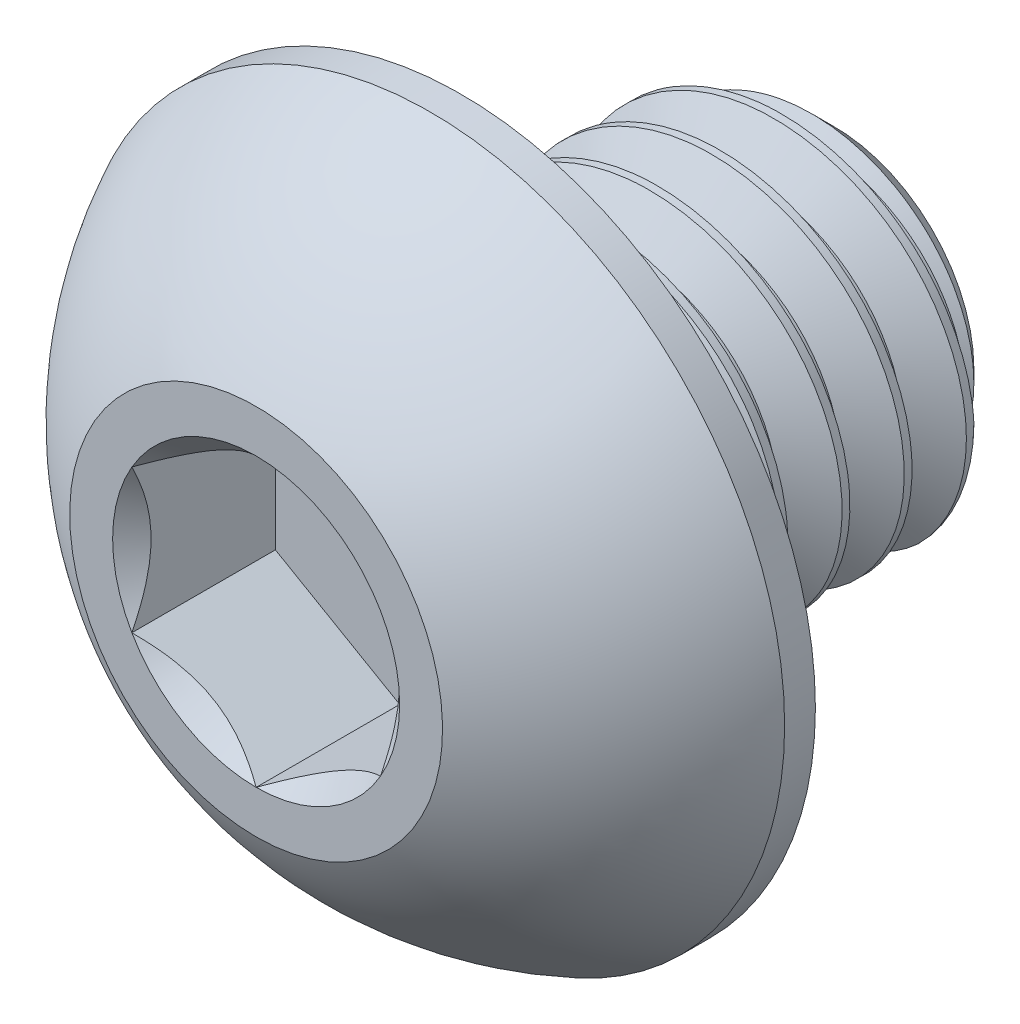
SolidWorks part; units mm, degrees
ref_plane "Front" through (0, 0, 0) normal (0, 0, 1) x (1, 0, 0)
ref_plane "Top" through (0, 0, 0) normal (0, 1, 0) x (1, 0, 0)
ref_plane "Right" through (0, 0, 0) normal (1, 0, 0) x (0, 0, -1)
sketch "Sketch1" plane through (0, 0, 0) normal (1, 0, 0) x (0, 0, -1)
  line L2 (1.65, 1.5) -> (4.65, 1.5)
  line L3 (4.65, 1.5) -> (4.65, 0)
  line L4 (4.65, 0) -> (1.65, 0)
  line L6 (1.4025, 2.85) -> (1.65, 2.85) construction
  line L7 (4.65, 1.5) -> (4.65, -1.5) construction
  line L8 (0, 0) -> (1.65, 0) construction
  line L9 (1.65, 2.85) -> (1.65, -2.85) construction
  line L11 (1.65, 1.5) -> (1.65, 0)
  line L13 (0, 1) -> (0, -1) construction
  line L14 (0, 1) -> (0, 1.5) construction
  line L15 (4.6187, 1.5541) -> (4.8687, 1.1211) construction
  line L16 (4.8687, 1.1211) -> (5.1187, 1.5541) construction
  line L17 (5.1187, 1.5541) -> (4.6187, 1.5541) construction
  line L18 (4.65, 1.5) -> (5.0875, 1.5) construction
  line L19 (4.8687, 1.5541) -> (4.8687, 1.5) construction
  line L20 (4.8687, 1.5) -> (4.8687, 1.1752) construction
  line L21 (4.8687, 1.1752) -> (4.8687, 1.1211) construction
  line L22 (4.8375, 1.1752) -> (4.9, 1.1752)
  line L23 (4.6344, 1.5271) -> (5.1031, 1.5271)
  line L24 (4.9, 1.1752) -> (5.1031, 1.5271)
  line L25 (4.8375, 1.1752) -> (4.6344, 1.5271)
  line L26 (4.275, 1.5) -> (4.65, 1.125)
  arc A3 (0, 1.5) -> (1.4025, 2.85) centre (2.7948, 0) cw construction
  point P29 (4.8687, 1.5271)
  point P30 (3.4, -1.5)
  dimension "D1" = 0.2475
  dimension "Pitch" = 0.5
  dimension "D3" = 0.0625
  dimension "D2" = 0.375
  dimension "D4" = 45
  dimension "D5" = 1.25
sketch "Sketch10" plane through (0, 0, 0) normal (1, 0, 0) x (0, 0, -1)
  line L0 (4.275, 1.5) -> (4.65, 1.125) construction
  line L1 (4.275, 1.5) -> (4.65, 1.125)
  line L4 (4.65, 1.5) -> (1.65, 1.5)
  line L5 (4.65, 0) -> (4.65, 1.5)
  line L6 (1.65, 0) -> (4.65, 0)
  line L7 (1.65, 1.5) -> (1.65, 0)
  line L8 (4.275, 1.5) -> (1.65, 1.5)
  line L9 (4.65, 0) -> (4.65, 1.125)
  line L10 (1.65, 0) -> (4.65, 0)
  line L11 (1.65, 1.5) -> (1.65, 0)
  dimension "D1" = 0
revolve "Revolve3" add sketch "Sketch10" angle 360 about L8
sketch "Sketch7" plane through (0, 0, 0) normal (1, 0, 0) x (0, 0, -1)
  line L6 (1.4025, 2.85) -> (1.65, 2.85) construction
  line L8 (0, 0) -> (1.65, 0) construction
  line L11 (1.65, 2.85) -> (1.65, -2.85) construction
  line L12 (1.4025, 2.85) -> (1.65, 2.85)
  line L13 (0, 0) -> (1.65, 0)
  line L14 (0, 1) -> (0, -1) construction
  line L15 (1.65, 2.85) -> (1.65, 0)
  line L16 (0, 1.5) -> (0, 0)
  arc A2 (1.4025, 2.85) -> (0, 1.5) centre (2.7948, 0) ccw construction
  arc A3 (1.4025, 2.85) -> (0, 1.5) centre (2.7948, 0) ccw
revolve "Revolve2" add sketch "Sketch7" angle 360 mid plane about L13
sketch "Sketch5" plane through (0, 0, 0) normal (0, 0, 1) x (1, 0, 0)
  line L1 (1, -0.5774) -> (1, 0.5774)
  line L2 (1, 0.5774) -> (0, 1.1547)
  line L3 (0, 1.1547) -> (-1, 0.5774)
  line L4 (-1, 0.5774) -> (-1, -0.5774)
  line L5 (-1, -0.5774) -> (0, -1.1547)
  line L6 (0, -1.1547) -> (1, -0.5774)
  circle A0 centre (0, 0) radius 1 construction
extrude "Cut-Extrude2" cut sketch "Sketch5" against normal blind 1.155
sketch "Sketch6" plane through (0, 0, 0) normal (0, 0, 1) x (1, 0, 0)
  circle A0 centre (0, 0) radius 1.1547
extrude "Cut-Extrude3" cut sketch "Sketch6" against normal blind 1.155 draft 45
sketch "Sketch9" plane through (0, 0, -1.65) normal (0, 0, -1) x (-1, 0, 0)
  circle A0 centre (0, 0) radius 1.5 construction
  circle A4 centre (0, 0) radius 1.5
split "Split1" bodies to split 113 resulting bodies 123 124 split by face at (2.85, 0, -1.65)
sketch "Sketch11" plane through (0, 0, -4.65) normal (0, 0, -1) x (-1, 0, 0)
  circle A0 centre (0, 0) radius 1.5 construction
  circle A1 centre (0, 0) radius 1.5
curve "Helix/Spiral1" pitch 0.5 height 4.65 radius 1.5 centre (0, 0, -4.65) axis (0, 0, 1) start towards (0, 1, 0)
sketch "Sketch12" plane through (0, 0, 0) normal (1, 0, 0) x (0, 0, -1)
  line L0 (4.8375, 1.1752) -> (4.9, 1.1752) construction
  line L1 (4.9, 1.1752) -> (5.1031, 1.5271) construction
  line L2 (4.6344, 1.5271) -> (5.1031, 1.5271) construction
  line L3 (4.8375, 1.1752) -> (4.6344, 1.5271) construction
  line L4 (4.8375, 1.1752) -> (4.9, 1.1752)
  line L5 (4.9, 1.1752) -> (5.1031, 1.5271)
  line L6 (4.6344, 1.5271) -> (5.1031, 1.5271)
  line L7 (4.8375, 1.1752) -> (4.6344, 1.5271)
sweep "Cut-Sweep2" cut profiles "Sketch12" path "Helix/Spiral1" align with end faces yes
extrude "Boss-Extrude1" add sketch "Sketch9" along normal blind 10 draft 45
equation "\"D1@Cut-Extrude2\" = \"Head Ht@Sketch1\" * .7"
equation "\"D1@Sketch1\" = \"Head Ht@Sketch1\" * .15"
equation "\"D1@Cut-Extrude3\" = \"D1@Cut-Extrude2\""
equation "\"D3@Sketch1\" = \"Pitch@Sketch1\" / 8"
equation "\"D2@Sketch1\"=\"Pitch@Sketch1\"*0.75"
equation "\"D3@Helix/Spiral1\" = \"Lg@Sketch1\" + \"Head Ht@Sketch1\""
equation "\"D4@Helix/Spiral1\"=\"pitch@sketch1\""
equation "\"D5@Sketch1\"=\"Pitch@Sketch1\"*2.5"
